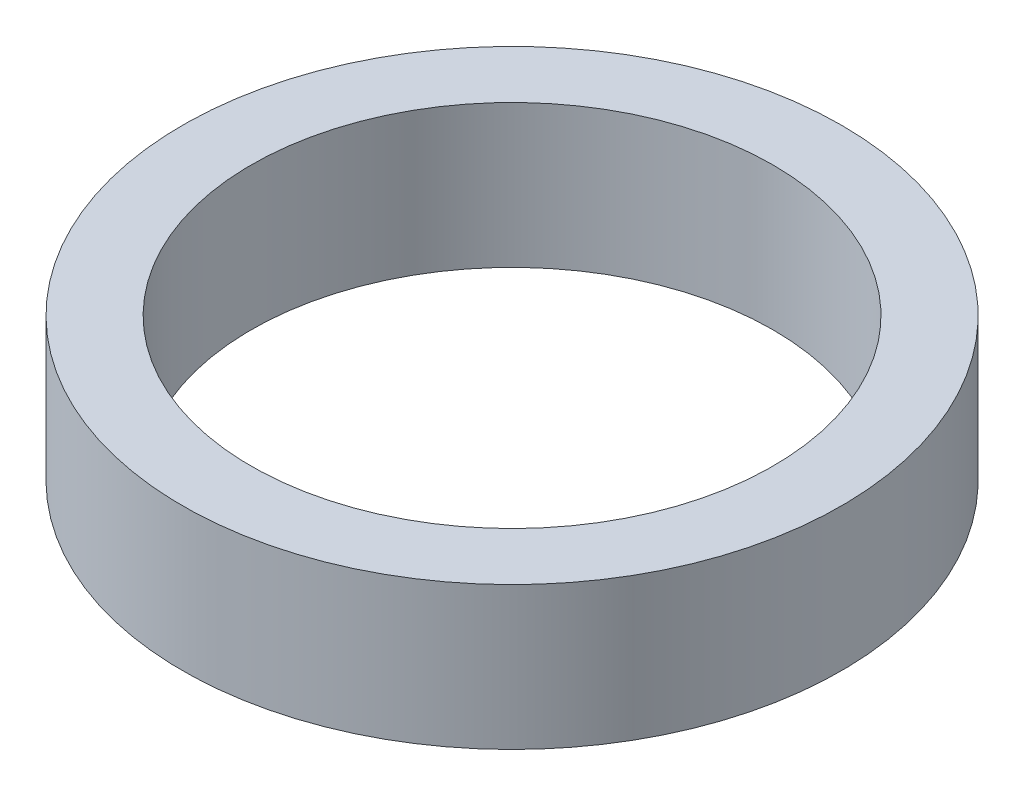
SolidWorks part; units mm, degrees
ref_plane "Front Plane" through (0, 0, 0) normal (0, 0, 1) x (1, 0, 0)
ref_plane "Top Plane" through (0, 0, 0) normal (0, 1, 0) x (1, 0, 0)
ref_plane "Right Plane" through (0, 0, 0) normal (1, 0, 0) x (0, 0, -1)
sketch "Sketch1" plane through (0, 0, 0) normal (0, 1, 0) x (1, 0, 0)
  circle A0 centre (0, 0) radius 60
  dimension "FLANGE_OD" = 120
extrude "Boss-Extrude1" add sketch "Sketch1" along normal blind 26
sketch "Sketch2" plane through (0, 0, 0) normal (0, 1, 0) x (1, 0, 0)
  circle A0 centre (0, 0) radius 47.5
  dimension "BORE_D" = 95
extrude "Cut-Extrude1" cut sketch "Sketch2" along normal through all
sketch "Sketch3" plane through (0, 26, 0) normal (0, 1, 0) x (1, 0, 0)
  circle A0 centre (0, 0) radius 25.5068 construction
  circle A1 centre (-25.5068, 0) radius 1.8747
  dimension "BOLT_D" = 3.7493
  dimension "BOLT_PCD" = 51.0135
extrude "Cut-Extrude2" cut sketch "Sketch3" against normal blind 15.9967 rebuild error yes
pattern_circular "CirPattern1" count 8 over 360 rebuild error yes
